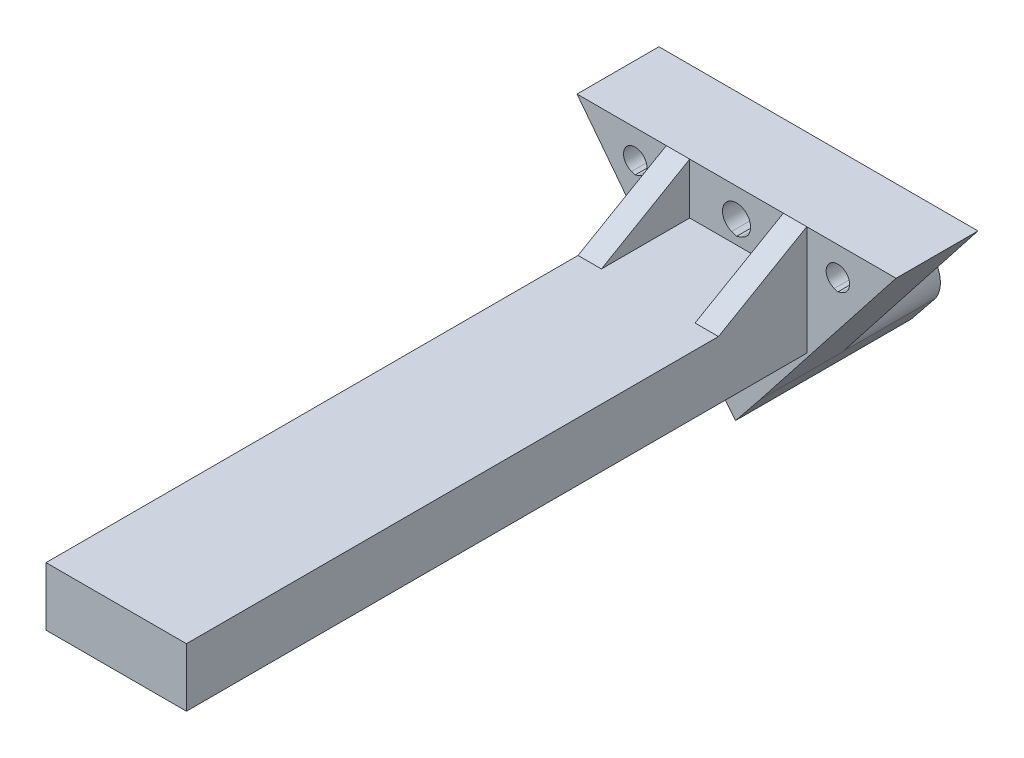
SolidWorks part; units mm, degrees
note: The reader was unsure of these and kept them because the rebuilt part matched: shared geometry of "Sketch5<3>".
ref_plane "Front Plane" through (0, 0, 0) normal (0, 0, 1) x (1, 0, 0)
ref_plane "Top Plane" through (0, 0, 0) normal (0, 1, 0) x (1, 0, 0)
ref_plane "Right Plane" through (0, 0, 0) normal (1, 0, 0) x (0, 0, -1)
sketch "Sketch1" plane through (0, 0, 0) normal (0, 1, 0) x (1, 0, 0)
  line L0 (-1.342, 19.5385) -> (-1.342, -40.4615) construction
  line L1 (-7.342, 19.5385) -> (4.658, 19.5385)
  line L2 (-7.342, 19.5385) -> (-7.342, -40.4615)
  line L3 (-7.342, -40.4615) -> (4.658, -40.4615)
  line L4 (4.658, 19.5385) -> (4.658, -40.4615)
  line L8 (-7.342, -10.4615) -> (4.658, -10.4615) construction
  dimension "D1" = 12
  dimension "D2" = 60
extrude "Boss-Extrude1" add sketch "Sketch1" along normal blind 1 contours L1 L4 L3 L2
sketch "Sketch4" plane through (0, 0, 0) normal (0, 1, 0) x (1, 0, 0)
  line L0 (-5.6775, -38.4615) -> (2.9083, -38.4615)
  line L1 (-6.3838, 2.2418) -> (-6.3846, 2.241)
  line L3 (3.6154, -37.7544) -> (3.6154, -29.1686)
  line L5 (-6.3846, 2.2426) -> (-6.3846, 2.241)
  line L6 (-5.6773, -28.4612) -> (-1.3898, -32.7493)
  line L7 (-2.0914, -3.461) -> (-6.3846, -7.7539)
  line L8 (-6.3846, -37.7544) -> (-6.3846, -29.1686)
  line L9 (-0.6778, -3.462) -> (3.6154, -7.755)
  line L10 (-6.3846, -27.7544) -> (-6.3846, -19.1681)
  line L11 (-6.3846, -17.7422) -> (-6.3846, -9.1682)
  line L12 (-1.3872, -12.7512) -> (2.9085, -8.461)
  line L13 (-2.0914, -3.461) -> (-6.3846, 0.8321)
  line L14 (-0.6783, 6.5389) -> (3.6154, 10.8326)
  line L15 (2.9129, 11.5385) -> (-5.6778, 11.5385)
  line L16 (3.6154, -27.7539) -> (3.6154, -19.1685)
  line L17 (-2.0915, -23.4612) -> (-6.3846, -19.1681)
  line L18 (-6.3846, -7.7539) -> (-6.3846, 0.8321)
  line L19 (3.6154, -7.755) -> (3.6154, 0.8312)
  line L20 (-6.3846, 2.2426) -> (-6.3846, 10.831)
  line L21 (-6.3846, -37.7544) -> (-2.0961, -33.4571)
  line L22 (-5.6775, -38.4615) -> (-1.3846, -34.1686)
  line L23 (2.9083, -38.4615) -> (-1.3846, -34.1686)
  line L24 (3.6154, -37.7544) -> (-0.7492, -33.5332)
  line L25 (-6.3846, -27.7544) -> (-2.0915, -23.4612)
  line L26 (-5.6773, -28.4612) -> (-1.3846, -24.1681)
  line L27 (2.899, -28.4517) -> (-1.3846, -24.1681)
  line L28 (-0.6773, -23.4612) -> (3.6154, -27.7539)
  line L29 (-6.3846, -17.7422) -> (-2.0948, -13.4579)
  line L30 (-5.677, -18.4616) -> (-1.3846, -14.1681)
  line L31 (2.9084, -18.4612) -> (-1.3846, -14.1681)
  line L32 (-0.6769, -13.4615) -> (3.6154, -17.7543)
  line L33 (-5.677, -8.4612) -> (-1.3846, -4.1678)
  line L35 (2.9085, -8.461) -> (-1.3846, -4.1678)
  line L36 (-0.6783, 6.5389) -> (3.6154, 2.2454)
  line L37 (-6.3838, 2.2418) -> (-2.0896, 6.536)
  line L38 (-5.6795, 1.5377) -> (-1.3854, 5.8318)
  line L39 (2.9082, 1.5382) -> (-1.3854, 5.8318)
  line L41 (-2.0961, -33.4571) -> (-6.3846, -29.1686)
  line L42 (-1.3844, -22.7541) -> (2.9084, -18.4612)
  line L43 (-0.7492, -33.5332) -> (3.6154, -29.1686)
  line L44 (3.6154, -17.7543) -> (3.6154, -9.1692)
  line L45 (-1.3898, -32.7493) -> (2.899, -28.4517)
  line L46 (-5.6778, 11.5385) -> (-1.3825, 7.2431)
  line L47 (-0.6769, -13.4615) -> (3.6154, -9.1692)
  line L48 (-1.3844, -22.7541) -> (-5.677, -18.4616)
  line L49 (-0.6773, -23.4612) -> (3.6154, -19.1685)
  line L52 (-2.0948, -13.4579) -> (-6.3846, -9.1682)
  line L53 (2.9082, 1.5382) -> (-1.3852, -2.7549)
  line L55 (-1.3872, -12.7512) -> (-5.677, -8.4612)
  line L56 (-0.6778, -3.462) -> (3.6154, 0.8312)
  line L58 (3.6154, 2.2454) -> (3.6154, 10.8326)
  line L61 (-1.3852, -2.7549) -> (-5.6795, 1.5377)
  line L66 (-1.3825, 7.2431) -> (2.9129, 11.5385)
  line L67 (-2.0896, 6.536) -> (-6.3846, 10.831)
extrude "Boss-Extrude5" add sketch "Sketch4" against normal blind 4
sketch "Sketch3" plane through (0, -4, 0) normal (0, -1, 0) x (1, 0, 0)
  line L0 (-1.342, 40.4615) -> (-1.342, -19.5385) construction
  line L1 (-7.342, 40.4615) -> (4.658, 40.4615) construction
  line L2 (-7.342, -19.5385) -> (4.658, -19.5385) construction
  line L3 (4.658, 10.4615) -> (-7.342, 10.4615) construction
  line L4 (4.658, -19.5385) -> (4.658, 40.4615) construction
  line L5 (-7.342, -19.5385) -> (-7.342, 40.4615) construction
  line L6 (3.658, 36.4615) -> (3.658, -9.9392)
  line L7 (-6.3846, 36.4615) -> (-6.3846, -9.9392)
  line L8 (-5.9846, 36.4615) -> (-6.3846, 36.4615)
  line L9 (3.658, 36.4615) -> (3.2154, 36.4615)
  line L10 (-5.9846, 36.4615) -> (-5.9846, -9.9392)
  line L11 (3.2154, 36.4615) -> (3.2154, -9.9392)
  line L13 (-5.6775, 38.4615) -> (2.9083, 38.4615) construction
  line L14 (3.658, -9.9392) -> (3.2154, -9.9392)
  line L15 (-5.9846, -9.9392) -> (-6.3846, -9.9392)
  dimension "D1" = 5
  dimension "D3" = 0.4
  dimension "D4" = 2
extrude "Cut-Extrude1" cut sketch "Sketch3" against normal blind 3
sketch "Sketch5" plane through (0, 0, -19.5385) normal (0, 0, -1) x (-1, 0, 0)
  line L0 (1.342, -4) -> (1.342, 17.9458) construction
  line L1 (7.342, -4) -> (-4.658, -4) construction
  line L2 (-4.658, 1) -> (-4.658, -4) construction
  line L3 (-4.658, -1.5) -> (7.342, -1.5) construction
  line L4 (-4.658, 1) -> (-4.658, -4) construction
  line L5 (7.342, 1) -> (7.342, -4) construction
  line L6 (-4.658, 1) -> (8.3846, 1)
  line L7 (-12.2888, 5.3559) -> (14.9728, 5.3559)
  line L8 (9.6927, 1.9661) -> (9.9994, 1.8577)
  line L9 (-7.6221, 1.9661) -> (-7.3154, 1.8577)
  line L10 (3.5374, -9.4159) -> (14.9728, 5.3559)
  line L11 (-12.2888, 5.3559) -> (-0.6898, -9.4092)
  line L12 (7.342, 1) -> (-4.658, 1) construction
  line L13 (-7.0087, 1.9661) -> (-7.3154, 1.8577)
  line L14 (1.342, 2.9179) -> (16.7595, 2.9179) construction
  line L15 (-0.6898, -9.4092) -> (1.4259, -12.0334)
  line L16 (10.3062, 1.9661) -> (9.9994, 1.8577)
  line L17 (3.5374, -9.4159) -> (1.4259, -12.0334)
  line L18 (0.9215, 1.794) -> (1.342, 1.6367)
  line L19 (1.342, 1.6367) -> (1.7626, 1.794)
  arc A0 (1.7626, 1.794) -> (0.9215, 1.794) centre (1.342, 2.9179) ccw
  arc A1 (10.3062, 1.9661) -> (9.6927, 1.9661) centre (9.9994, 2.9179) ccw
  arc A2 (-7.6221, 1.9661) -> (-7.0087, 1.9661) centre (-7.3154, 2.9179) cw
  arc A3 (3.5374, -9.4159) -> (-0.6898, -9.4092) centre (1.4259, -8.0773) ccw
  dimension "D1" = 2.4
  dimension "D2" = 2
  dimension "D5" = 5
extrude "Boss-Extrude6" add sketch "Sketch5" against normal blind 7
extrude "Boss-Extrude11" add sketch "Sketch5<3>" along normal blind 8 contours L17 A3 L15
sketch "Sketch5<3>" plane through (0, 0, -19.5385) normal (0, 0, -1) x (-1, 0, 0) same geometry as "Sketch5"
sketch "Sketch11" plane through (-7.342, 0, 0) normal (-1, 0, 0) x (0, 0, 1)
  line L0 (-12.5385, 5.3559) -> (-4.9938, 1)
  line L3 (-12.5385, 1) -> (40.4615, 1) construction
  line L4 (-4.9938, 1) -> (-12.5385, 1)
  line L5 (-12.5385, -9.4159) -> (-12.5385, 5.3559) construction
  line L6 (-12.5385, 1) -> (-12.5385, 5.3559)
  dimension "D1" = 60
extrude "Boss-Extrude12" add sketch "Sketch11" against normal blind 2
ref_plane "Plane1" through (-1.342, 0, 0) normal (-1, 0, 0) x (0, 0, 1)
sketch "Sketch12" plane through (-1.342, 0, 0) normal (-1, 0, 0) x (0, 0, 1)
  line L0 (-13.8591, -4.4186) -> (-13.8591, -9.6832)
  line L1 (-13.8591, -9.6832) -> (-6.411, -3.8889)
  line L2 (-6.411, -3.8889) -> (-6.411, 0.3167)
  line L3 (-6.411, 0.3167) -> (-13.8591, 0.3167)
  line L4 (-13.8591, 0.3167) -> (-13.8591, -4.4186)
  line L5 (-13.8591, -4.4186) -> (-12.4258, -4.4186)
extrude "Boss-Extrude13" add sketch "Sketch12" along normal mid plane 1.5
sketch "Sketch14" plane through (4.658, 0, 0) normal (1, 0, 0) x (0, 0, -1)
  line L0 (4.9938, 1) -> (12.5385, 5.3559)
  line L1 (12.5385, 5.3559) -> (12.5385, 1)
  line L2 (12.5385, 5.3559) -> (12.5385, -9.4092) construction
  line L3 (12.5385, 5.3559) -> (12.5385, 1) construction
  line L4 (12.5385, 1) -> (4.9938, 1)
extrude "Boss-Extrude15" add sketch "Sketch14" against normal blind 2
